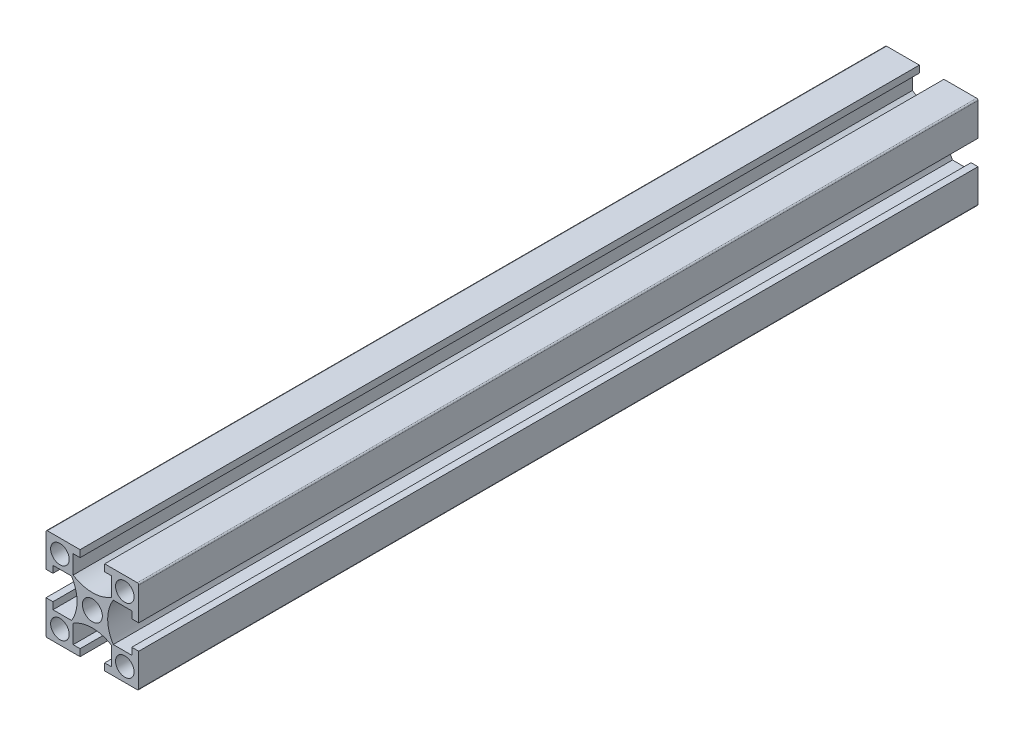
SolidWorks part; units mm, degrees
material "3.0255 (EN-AW 1350A)"
ref_plane "정면" through (0, 0, 0) normal (0, 0, 1) x (1, 0, 0)
ref_plane "윗면" through (0, 0, 0) normal (0, 1, 0) x (1, 0, 0)
ref_plane "우측면" through (0, 0, 0) normal (1, 0, 0) x (0, 0, -1)
sketch "스케치1" plane through (0, 0, 0) normal (0, 0, 1) x (1, 0, 0)
  line L0 (0, 32.0265) -> (0, -31.6588) construction
  line L1 (-10, 10) -> (-10, -10)
  line L2 (-10, 10) -> (10, 10)
  line L3 (-10, 2.65) -> (-8.5, 2.65)
  line L4 (13.6618, 0) -> (-11.6993, 0) construction
  line L5 (-8.5, 2.65) -> (-8.5, 4.15)
  line L6 (-8.5, 4.15) -> (-4.5032, 4.15)
  line L7 (-10, -2.65) -> (-8.5, -2.65)
  line L8 (-8.5, -2.65) -> (-8.5, -4.15)
  line L9 (-8.5, -4.15) -> (-4.5032, -4.15)
  line L10 (-10, -10) -> (10, -10)
  line L11 (10, 10) -> (10, -10)
  circle A0 centre (-7, 7) radius 2
  circle A1 centre (-7, -7) radius 2
  arc A2 (-4.5032, 4.15) -> (-4.5032, -4.15) centre (-11.0587, 0) cw
  circle A3 centre (0, 0) radius 2.15
  circle A4 centre (7, 7) radius 2
  circle A5 centre (7, -7) radius 2
  point P21 (-10, 0)
  point P23 (-3.3, 0)
  point P31 (0, -10)
  point P32 (0, 10)
  dimension "D3" = 4
  dimension "D9" = 6.7
  dimension "D10" = 4.3
  dimension "D11" = 7.7587
  dimension "D1" = 20
  dimension "D2" = 20
  dimension "D4" = 14
  dimension "D5" = 14
  dimension "D6" = 5.3
  dimension "D7" = 8.3
  dimension "D8" = 1.5
extrude "보스-돌출1" add sketch "스케치1" along normal blind 181 contours A0 | A4 | A3 | A5 | A1 | A2 L6 L5 L3 L1 L7 L8 L9 | L2 L11 L10 L1 region at (-6.6069, 0, 0) region at (-7, 7, 0) region at (-7, -7, 0) region at (0, 0, 0) region at (7, 7, 0) region at (7, -7, 0)
extrude "컷-돌출1" cut sketch "스케치1<3>" along normal up to next contours A2 L6 L5 L3 L1 L7 L8 L9 region at (-6.6069, 0, 0)
sketch "스케치1<3>" plane through (0, 0, 0) normal (0, 0, 1) x (1, 0, 0) same geometry as "스케치1"
pattern_circular "원형 패턴1" count 4 over 360 about axis through (0, 0, 181) along (0, 0, -1) of "컷-돌출1" reverse direction yes
fillet "필렛1" radius 0.3 4 edges at (10, -10, 90.5) (-10, -10, 90.5) (-10, 10, 90.5) (10, 10, 90.5)
sketch "스케치2" plane through (-10, 0, 0) normal (-1, 0, 0) x (0, 0, 1)
  line L0 (0, 4.15) -> (0, -4.15) construction
  line L1 (181, -4.15) -> (181, 4.15) construction
  circle A1 centre (11, 0) radius 2.5
  circle A2 centre (172, 0) radius 2.5
  dimension "D1" = 11
  dimension "D2" = 9
extrude "컷-돌출2" cut sketch "스케치2" against normal through all
